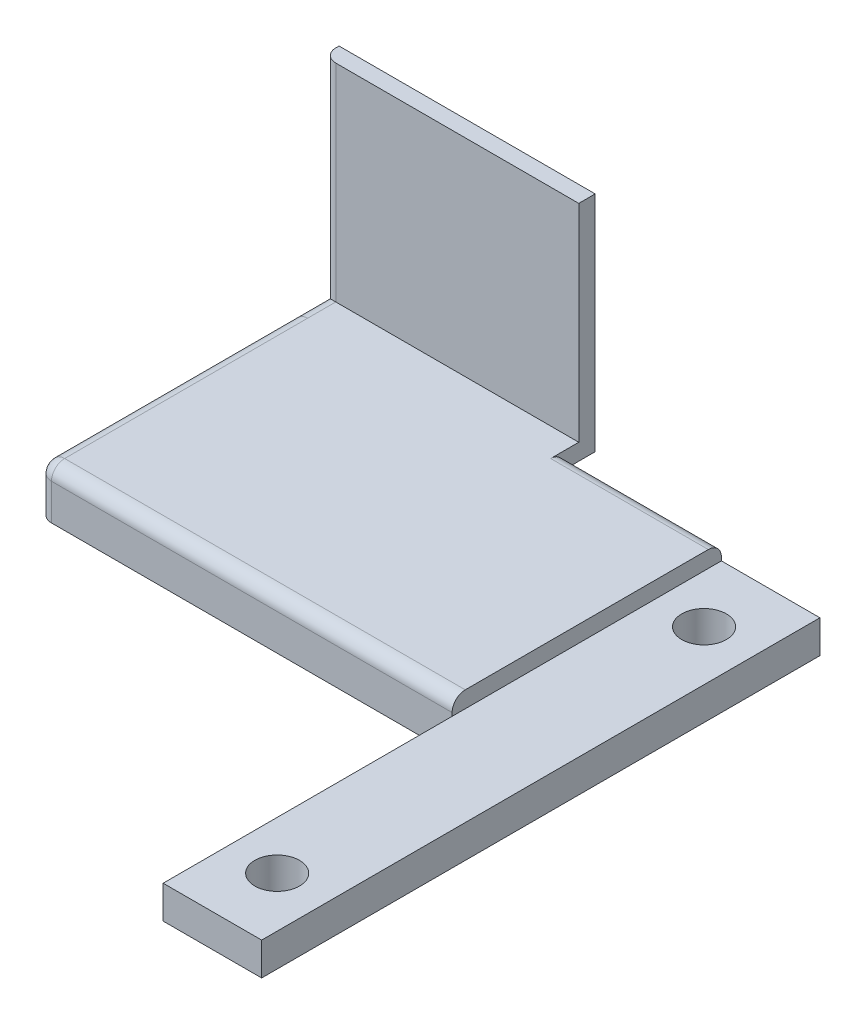
SolidWorks part; units mm, degrees
ref_plane "前视基准面" through (0, 0, 0) normal (0, 0, 1) x (1, 0, 0)
ref_plane "上视基准面" through (0, 0, 0) normal (0, 1, 0) x (1, 0, 0)
ref_plane "右视基准面" through (0, 0, 0) normal (1, 0, 0) x (0, 0, -1)
other "Configuration Table"
sketch "草图1" plane through (0, 0, 0) normal (0, 1, 0) x (1, 0, 0)
  line L1 (0, 0) -> (40, 0)
  line L2 (0, 0) -> (0, -85)
  line L3 (0, -85) -> (40, -85)
  line L4 (40, 0) -> (40, -85)
  dimension "D1" = 85
  dimension "D2" = 40
extrude "凸台-拉伸1" add sketch "草图1" along normal blind 5
sketch "草图2" plane through (0, 5, 0) normal (0, 1, 0) x (1, 0, 0)
  line L1 (0, -85) -> (25, -85)
  line L2 (0, -85) -> (0, 0)
  line L3 (0, 0) -> (25, 0)
  line L4 (25, -85) -> (25, 0)
  dimension "D1" = 25
extrude "凸台-拉伸2" add sketch "草图2" along normal blind 2.5
sketch "草图3" plane through (0, 5, 0) normal (0, 1, 0) x (1, 0, 0)
  line L0 (25, -85) -> (40, -85) construction
  circle A0 centre (32.3611, -75) radius 3.4
  dimension "D1" = 6.8
  dimension "D2" = 10
sketch "草图5" plane through (0, 0, 0) normal (0, -1, 0) x (1, 0, 0)
  line L0 (0, 85) -> (40, 85) construction
  line L1 (0, 0) -> (-38, 0)
  line L2 (0, 0) -> (0, 85)
  line L3 (0, 85) -> (-38, 85)
  line L4 (-38, 0) -> (-38, 85)
  dimension "D1" = 38
extrude "凸台-拉伸3" add sketch "草图5" against normal up to surface (7.5 mm away) up to face at (12.5, 7.5, 42.5)
extrude "切除-拉伸1" cut sketch "草图3" against normal through all
sketch "草图6" plane through (0, 5, 0) normal (0, 1, 0) x (1, 0, 0)
  line L0 (32.3611, -75) -> (32.3611, -27.183) construction
  line L1 (40, 0) -> (25, 0) construction
  circle A0 centre (32.3611, -10) radius 3.4
  dimension "D1" = 6.8
  dimension "D2" = 10
extrude "切除-拉伸2" cut sketch "草图6" against normal through all
fillet "圆角1" radius 2 2 edges at (-6.5, 7.5, 85) (-38, 7.5, 42.5)
fillet "圆角2" radius 2 5 edges at (-37.4142, 6.9142, 84.4142) (-38, 2.75, 0) (-38, 2.75, 85) (-5.5, 7.5, 0) (-37.4142, 6.9142, 0)
sketch "草图7" plane through (0, 0, 85) normal (0, 0, 1) x (1, 0, 0)
  line L0 (25, 5.5) -> (25, 7.5) construction
  line L1 (-38, 0) -> (25, 0)
  line L2 (-38, 0) -> (-38, 17.9865)
  line L3 (-38, 17.9865) -> (25, 17.9865)
  line L4 (25, 0) -> (25, 17.9865)
extrude "切除-拉伸3" cut sketch "草图7" against normal blind 44
fillet "圆角3" radius 2 3 edges at (-38, 2.75, 41) (-37.4142, 6.9142, 41) (-5.5, 7.5, 41)
sketch "草图8" plane through (-38, 0, 0) normal (-1, 0, 0) x (0, 0, 1)
  line L0 (2, 7.5) -> (39, 7.5) construction
  line L1 (2, 5) -> (-4.7841, 5)
  line L2 (2, 5) -> (2, 7.5)
  line L3 (2, 7.5) -> (-2.2841, 7.5)
  line L4 (-4.7841, 5) -> (-4.7841, 7.573)
  line L6 (-4.7841, 5) -> (-1.3921, 5)
  line L7 (-4.7841, 5) -> (-4.7841, 39)
  line L8 (-4.7841, 39) -> (-2.2841, 39)
  line L9 (-2.2841, 7.5) -> (-2.2841, 39)
  point P11 (0, 0)
  line M9 (2, 5.5) -> (2, 0)
  dimension "D1" = 2.5
  dimension "D2" = 2.5
  dimension "D3" = 31.5
extrude "凸台-拉伸4" add sketch "草图8" against normal blind 39 contours L3 L9 L8 L7 L4 L1 L2 M9 region at (-38, 20.2375, -3.1546)
fillet "圆角4" radius 2 2 edges at (-38, 23.25, -2.2841) (-38, 7.5, -0.1421)
